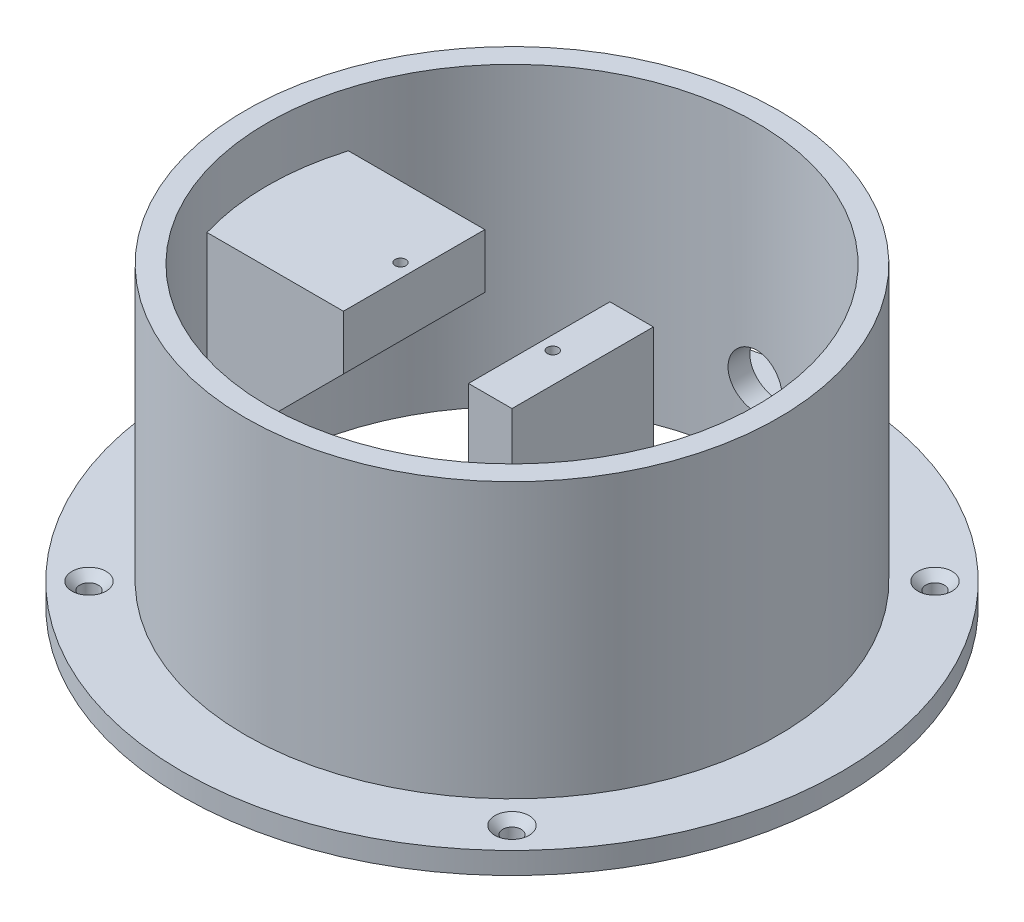
SolidWorks part; units mm, degrees
ref_plane "Front Plane" through (0, 0, 0) normal (0, 0, 1) x (1, 0, 0)
ref_plane "Top Plane" through (0, 0, 0) normal (0, 1, 0) x (1, 0, 0)
ref_plane "Right Plane" through (0, 0, 0) normal (1, 0, 0) x (0, 0, -1)
sketch "Sketch1" plane through (0, 0, 0) normal (0, 1, 0) x (1, 0, 0)
  circle A0 centre (0, 0) radius 60.625
  circle A1 centre (0, 0) radius 45
  dimension "D1" = 121.25
  dimension "D2" = 90
extrude "Boss-Extrude1" add sketch "Sketch1" along normal blind 4
sketch "Sketch2" plane through (0, 4, 0) normal (0, 1, 0) x (1, 0, 0)
  circle A0 centre (0, 0) radius 45 construction
  circle A1 centre (0, 0) radius 45
  circle A2 centre (0, 0) radius 49
  dimension "D1" = 4
extrude "Boss-Extrude2" add sketch "Sketch2" along normal blind 50.5
ref_plane "Plane1" through (0, 34.5, 0) normal (0, 1, 0) x (1, 0, 0)
sketch "Sketch4" plane through (0, 0, 0) normal (0, 0, 1) x (1, 0, 0)
  line L0 (-60.625, 0) -> (60.625, 0) construction
  line L1 (5, 44.5) -> (13, 44.5)
  line L2 (5, 44.5) -> (5, 0)
  line L3 (5, 0) -> (13, 0)
  line L4 (13, 44.5) -> (13, 0)
  line L5 (49, 54.5) -> (-49, 54.5) construction
  line L6 (-45, 54.5) -> (-45, 4)
  line L7 (-18, 44.5) -> (-45, 44.5)
  line L8 (-18, 44.5) -> (-18, 34.5)
  line L9 (-18, 34.5) -> (-45, 34.5)
  line L10 (-45, 44.5) -> (-45, 34.5)
  line L11 (60.625, 4) -> (-60.625, 4) construction
  line L12 (-18, 34.5) -> (-45, 7.5)
  dimension "D1" = 5
  dimension "D2" = 8
  dimension "D3" = 10
  dimension "D4" = 23
  dimension "D5" = 27
  dimension "D6" = 10
  dimension "D7" = 45
  dimension "D8" = 10
extrude "Boss-Extrude4" add sketch "Sketch4" along normal mid plane 26 contours L9 L8 L7 L6 | L12 L9 L6 | L1 L4 L3 L2 region at (-31.5, 39.5, 0) region at (-36, 25.5, 0)
sketch "Sketch5" plane through (0, 0, 0) normal (0, -1, 0) x (1, 0, 0)
  line L0 (3.3931, 14.5721) -> (34.8417, 28.479)
  line L1 (3.3931, -12.7877) -> (35.3292, -27.872)
  line L2 (3.3931, 14.5721) -> (3.3931, -12.7877)
  circle A0 centre (0, 0) radius 45 construction
  arc A1 (35.3292, -27.872) -> (34.8417, 28.479) centre (0, 0) ccw
extrude "Boss-Extrude5" add sketch "Sketch5" against normal up to surface (4 mm away) contours L0 A1 L1 L2 up to face at (0, 4, 60.625)
sketch "Sketch7" plane through (0, 44.5, 0) normal (0, 1, 0) x (1, 0, 0)
  line L0 (-18, -13) -> (-18, 13) construction
  circle A0 centre (-20.5, 5) radius 1.3
  circle A1 centre (-20.5, -5) radius 1.3
  circle A2 centre (27.5, 5) radius 1.3
  circle A3 centre (27.5, -5) radius 1.3
  dimension "D1" = 2.6
  dimension "D2" = 2.6
  dimension "D3" = 10
  dimension "D4" = 5
  dimension "D5" = 2.5
  dimension "D7" = 48
  dimension "D6" = 2
sketch "Sketch12" plane through (0, 4, 0) normal (0, 1, 0) x (1, 0, 0)
  line L3 (11.3931, 7.7188) -> (11.3931, -9.3624)
  line L4 (11.3931, 7.7188) -> (11.3931, -9.3624)
  line L9 (18, 10.8394) -> (18, -12.2841)
  line L10 (13, -13) -> (13, 13) construction
  line L18 (11.3931, -9.3624) -> (32.0457, -18.4953)
  line L19 (32.4985, 17.6875) -> (11.3931, 7.7188)
  line L21 (18, -12.2841) -> (32.0457, -18.4953)
  line L22 (32.4985, 17.6875) -> (18, 10.8394)
  arc A2 (32.0457, -18.4953) -> (32.4985, 17.6875) centre (0, 0) ccw
  arc A3 (32.0457, -18.4953) -> (32.4985, 17.6875) centre (0, 0) ccw
  dimension "D2" = 5
  dimension "D1" = 8
extrude "Cut-Extrude9" cut sketch "Sketch12" against normal through all contours L21 A3 L22 | L22 L9 L21 region at (27.4858, 4, 0.4769)
sketch "Sketch14" plane through (0, 4, 0) normal (0, 1, 0) x (1, 0, 0)
  line L0 (0, 0) -> (-38.8909, 38.8909) construction
  line L1 (5, 13) -> (13, 13) construction
  circle A0 centre (-38.8909, 38.8909) radius 1.5
  circle A1 centre (38.8909, 38.8909) radius 1.5
  circle A2 centre (38.8909, -38.8909) radius 1.5
  circle A3 centre (-38.8909, -38.8909) radius 1.5
  point P15 (0, 0)
  dimension "D1" = 3
  dimension "D2" = 55
  dimension "D3" = 135
  dimension "D4" = 4
hole_wizard "CSK for M3 Countersunk Flat Head Screw1" positions "Sketch15" profile "Sketch17" countersink size "M3" standard "DIN" end condition up to next
sketch "Sketch15" plane through (0, 4, 0) normal (0, 1, 0) x (1, 0, 0)
  point P0 (-38.8909, 38.8909)
  point P3 (-38.8909, -38.8909)
  point P6 (38.8909, -38.8909)
  point P9 (38.8909, 38.8909)
sketch "Sketch17" plane through (-38.8909, 4, -38.8909) normal (1, 0, 0) x (0, 0, 1)
  line L0 (0, 0) -> (0, 4)
  line L1 (0, 4) -> (1.7, 4)
  line L2 (1.7, 4) -> (1.7, 1.45)
  line L3 (1.7, 1.45) -> (3.15, 0)
  line L5 (3.15, 0) -> (0, 0)
  line L6 (-1.7, 1.45) -> (-3.15, 0) construction
  line L11 (0, -6.35) -> (0, 107.95) construction
  dimension "Thru Hole Dia." = 3.4
  dimension "Thru Hole Depth" = 4
  dimension "Near C'Sink Dia." = 6.3
  dimension "Near C'Sink Angle" = 90
sketch "Sketch18" plane through (0, 44.5, 0) normal (0, 1, 0) x (1, 0, 0)
  line L0 (-18, -13) -> (-18, 13) construction
  line L1 (5, -13) -> (5, 13) construction
  circle A0 centre (-20.5, 0) radius 1
  circle A1 centre (7.5, 0) radius 1
  point P4 (-18, 0)
  dimension "D1" = 2.5
  dimension "D2" = 2.5
extrude "Cut-Extrude10" cut sketch "Sketch18" against normal blind 4.5 contours A0
extrude "Cut-Extrude11" cut sketch "Sketch18<3>" against normal blind 4.5
sketch "Sketch18<3>" plane through (0, 44.5, 0) normal (0, 1, 0) x (1, 0, 0) same geometry as "Sketch18"
sketch "Sketch19" plane through (0, 0, 0) normal (0, 0, 1) x (1, 0, 0)
  circle A0 centre (0, 13.2905) radius 5
  dimension "D1" = 10
extrude "Cut-Extrude12" cut sketch "Sketch19" against normal blind 50
